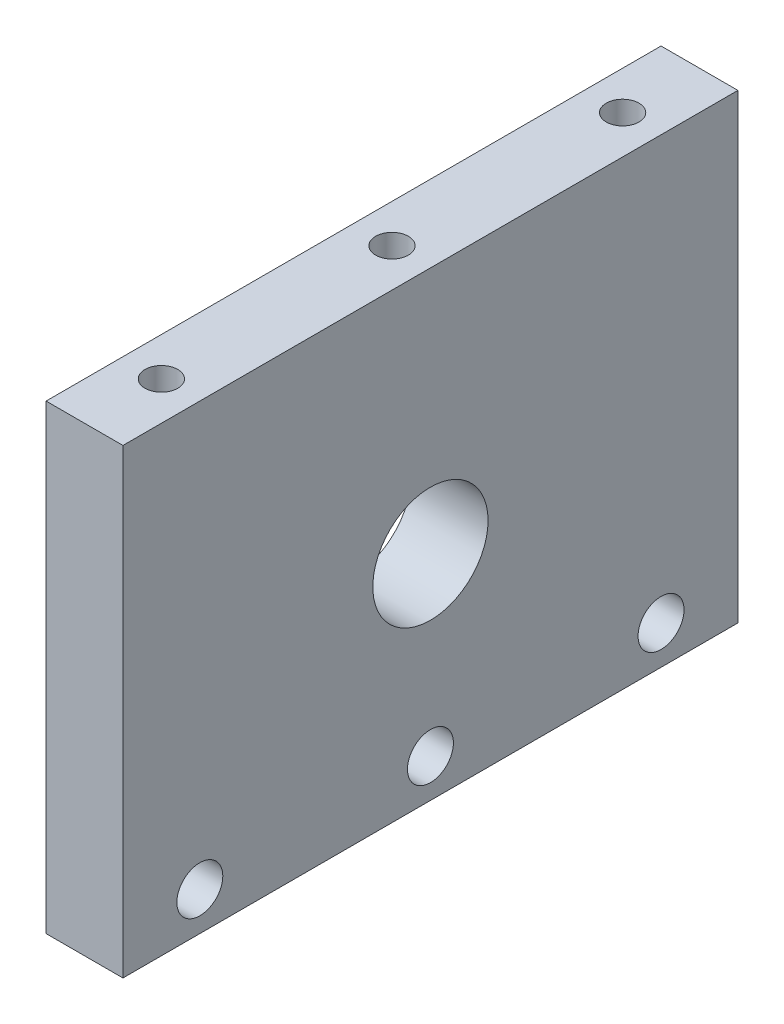
SolidWorks part; units mm, degrees
ref_plane "Front Plane" through (0, 0, 0) normal (0, 0, 1) x (1, 0, 0)
ref_plane "Top Plane" through (0, 0, 0) normal (0, 1, 0) x (1, 0, 0)
ref_plane "Right Plane" through (0, 0, 0) normal (1, 0, 0) x (0, 0, -1)
sketch "Sketch1" plane through (0, 0, 0) normal (1, 0, 0) x (0, 0, -1)
  line L1 (0, 0) -> (-50.8, 0)
  line L2 (0, 0) -> (0, 38.1)
  line L3 (0, 38.1) -> (-50.8, 38.1)
  line L4 (-50.8, 0) -> (-50.8, 38.1)
  dimension "D1" = 38.1
  dimension "D2" = 50.8
extrude "Boss-Extrude1" add sketch "Sketch1" along normal blind 6.35
sketch "Sketch2" plane through (0, 38.1, 0) normal (0, 1, 0) x (1, 0, 0)
  line L0 (0, 0) -> (0, -50.8) construction
  line L1 (6.35, -50.8) -> (0, -50.8) construction
  circle A0 centre (3.175, -44.45) radius 1.7526
  circle A1 centre (3.175, -6.35) radius 1.7526
  circle A3 centre (3.175, -25.4) radius 1.7526
  dimension "D1" = 3.5052
  dimension "D3" = 3.5052
  dimension "D5" = 3.5052
  dimension "D2" = 3.175
  dimension "D4" = 6.35
  dimension "D6" = 25.4
  dimension "D7" = 44.45
sketch "Sketch3" plane through (6.35, 0, 0) normal (1, 0, 0) x (0, 0, -1)
  line L0 (-50.8, 38.1) -> (-50.8, 0) construction
  line L1 (-50.8, 0) -> (0, 0) construction
  circle A0 centre (-44.45, 3.175) radius 1.8986
  circle A1 centre (-25.4, 3.175) radius 1.8986
  circle A2 centre (-6.35, 3.175) radius 1.8987
  dimension "D7" = 3.7973
  dimension "D8" = 3.7973
  dimension "D9" = 3.7973
  dimension "D1" = 6.35
  dimension "D2" = 25.4
  dimension "D3" = 44.45
  dimension "D4" = 3.175
  dimension "D5" = 3.175
  dimension "D6" = 3.175
extrude "Cut-Extrude1" cut sketch "Sketch3" against normal blind 6.35
hole_wizard "#6-32 Tapped Hole1" positions "Sketch10" profile "Sketch11" tap size "#6-32" standard "ANSI Inch"
sketch "Sketch10" plane through (0, 38.1, 0) normal (0, 1, 0) x (1, 0, 0)
  point P0 (3.175, -6.35)
  point P3 (3.175, -25.4)
  point P6 (3.175, -44.45)
sketch "Sketch11" plane through (3.175, 38.1, 6.35) normal (1, 0, 0) x (0, 0, 1)
  line L0 (0, 0) -> (0, 12.7)
  line L1 (0, 12.7) -> (1.3525, 11.8873)
  line L2 (1.3525, 11.8873) -> (1.3525, 0)
  line L5 (1.3525, 0) -> (0, 0)
  line L10 (0, 12.7) -> (-1.3526, 11.8873) construction
  line L11 (0, -6.35) -> (0, 107.95) construction
  dimension "Tap Drill Dia." = 2.7051
  dimension "Tap Drill Depth" = 12.7
  dimension "Drill Angle" = 118
cosmetic thread "Hole Thread1" parameters "D1"=10.16, "D2"=3.5052
cosmetic thread "Hole Thread2" parameters "D1"=10.16, "D2"=3.5052
cosmetic thread "Hole Thread3" parameters "D1"=10.16, "D2"=3.5052
sketch "Sketch12" plane through (6.35, 0, 0) normal (1, 0, 0) x (0, 0, -1)
  line L0 (-50.8, 0) -> (0, 0) construction
  line L1 (-50.8, 38.1) -> (-50.8, 0) construction
  circle A0 centre (-25.4, 17.653) radius 4.7625
  dimension "D1" = 9.525
  dimension "D2" = 17.653
  dimension "D3" = 25.4
extrude "Cut-Extrude3" cut sketch "Sketch12" against normal blind 6.35
